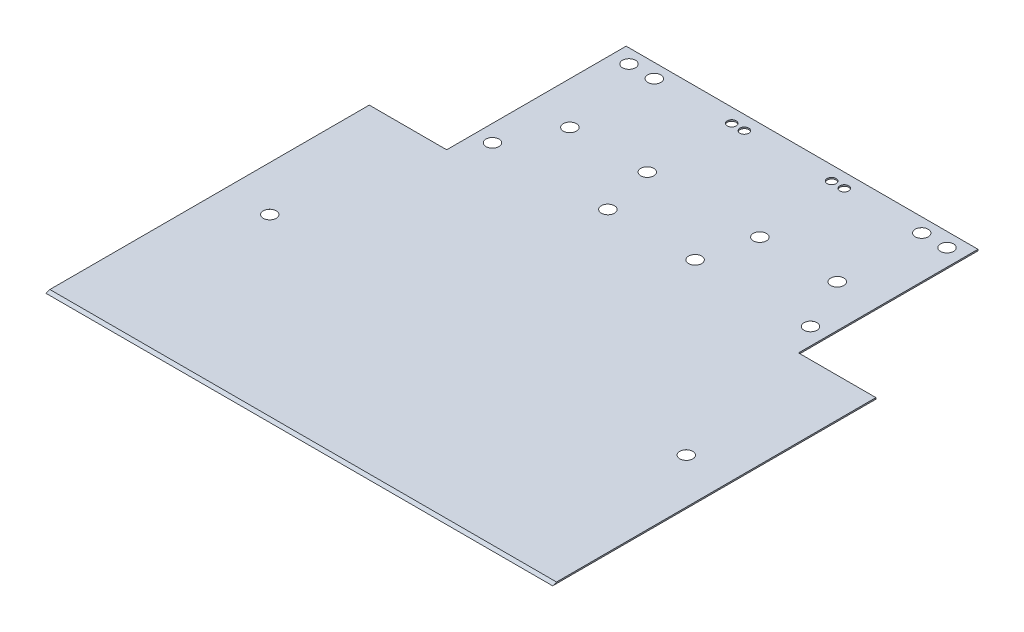
SolidWorks part; units mm, degrees
ref_plane "Alzado" through (0, 0, 0) normal (0, 0, 1) x (1, 0, 0)
ref_plane "Planta" through (0, 0, 0) normal (0, 1, 0) x (1, 0, 0)
ref_plane "Vista lateral" through (0, 0, 0) normal (1, 0, 0) x (0, 0, -1)
sketch "Croquis2" plane through (0, 0, 0) normal (0, 1, 0) x (1, 0, 0)
  line L0 (-90, 25.54) -> (-62.5, 25.54)
  line L1 (90, -89.31) -> (-90, -89.31)
  line L2 (90, -89.31) -> (90, 25.54)
  line L3 (62.5, 89.31) -> (-62.5, 89.31)
  line L4 (-90, -89.31) -> (-90, 25.54)
  line L5 (90, -89.31) -> (-62.5, 62.0208) construction
  line L6 (62.5, 62.0208) -> (-90, -89.31) construction
  line L7 (-62.5, 25.54) -> (-62.5, 89.31)
  line L8 (0, 0) -> (0, 89.31) construction
  line L9 (90, 25.54) -> (62.5, 25.54)
  line L10 (62.5, 25.54) -> (62.5, 89.31)
  point P0 (0, 0)
  dimension "D1" = 125
  dimension "D2" = 180
  dimension "D4" = 63.77
extrude "Saliente-Extruir1" add sketch "Croquis2" along normal blind 0.5
sketch "Croquis3" plane through (90, 0, 0) normal (1, 0, 0) x (0, 0, -1)
  line L0 (-89.31, 0) -> (-87.9363, 0.5)
  line L1 (-89.31, 0.5) -> (25.54, 0.5) construction
  line L2 (-87.9363, 0.5) -> (-89.31, 0.5)
  line L3 (-89.31, 0.5) -> (-89.31, 0)
  dimension "D1" = 70
sketch "Croquis5" plane through (0, 0.5, 0) normal (0, 1, 0) x (1, 0, 0)
  circle A0 centre (74, -25.8204) radius 1.585
sketch "Croquis6" plane through (0, 0.5, 0) normal (0, 1, 0) x (1, 0, 0)
  circle A0 centre (-56.5, 35.81) radius 1.585
  circle A1 centre (-15.5, 35.81) radius 1.585
  circle A2 centre (-15.5, 84.31) radius 1.585
  circle A3 centre (-56.5, 84.31) radius 1.585
extrude "Cortar-Extruir4" cut sketch "Croquis6" against normal up to next
sketch "Croquis7" plane through (0, 0.5, 0) normal (0, 1, 0) x (1, 0, 0)
  circle A0 centre (56.5, 35.81) radius 1.585
  circle A1 centre (15.5, 35.81) radius 1.585
  circle A2 centre (15.5, 84.31) radius 1.585
  circle A3 centre (56.5, 84.31) radius 1.585
extrude "Cortar-Extruir5" cut sketch "Croquis7" against normal up to next
mirror "Simetría3" about plane through (0, 0, 0) normal (1, 0, 0) of "Saliente-Extruir1"
sketch "Croquis8" plane through (0, 0.5, 0) normal (0, 1, 0) x (1, 0, 0)
  circle A0 centre (-20, 54.31) radius 1.585
  circle A1 centre (-47.5, 54.31) radius 1.585
  circle A2 centre (-47.5, 84.31) radius 1.585
  circle A3 centre (-20, 84.31) radius 1.585
extrude "Cortar-Extruir6" cut sketch "Croquis8" against normal up to next
mirror "Simetría4" about plane through (0, 0, 0) normal (1, 0, 0) of "Cortar-Extruir6"
sketch "Croquis9" plane through (0, 0, 0) normal (0, -1, 0) x (1, 0, 0)
  circle A0 centre (56.5, -35.81) radius 1.585
  circle A2 centre (15.5, -35.81) radius 1.585
  circle A3 centre (15.5, -84.31) radius 1.585
  circle A4 centre (56.5, -84.31) radius 1.585
extrude "Cortar-Extruir7" cut sketch "Croquis9" against normal up to next
mirror "Simetría5" about plane through (0, 0, 0) normal (1, 0, 0) of "Cortar-Extruir7"
extrude "Cortar-Extruir8" cut sketch "Croquis5" against normal up to next
mirror "Simetría6" about plane through (0, 0, 0) normal (1, 0, 0) of "Cortar-Extruir8"
extrude "Cortar-Extruir9" cut sketch "Croquis3" against normal up to next
sketch "Croquis11" plane through (0, 0, 0) normal (0, -1, 0) x (1, 0, 0)
  circle A0 centre (-74, 25.8204) radius 3.03
  circle A1 centre (-56.5, -35.81) radius 3.03
  circle A2 centre (-15.5, -35.81) radius 3.03
  circle A3 centre (-20, -54.31) radius 3.03
  circle A4 centre (-47.5, -54.31) radius 3.03
  circle A5 centre (-47.5, -84.31) radius 3.03
  circle A6 centre (-56.5, -84.31) radius 3.03
  dimension "D1" = 6.06
  dimension "D2" = 6.06
  dimension "D3" = 6.06
  dimension "D4" = 6.06
  dimension "D5" = 6.06
  dimension "D6" = 6.06
  dimension "D7" = 6.06
extrude "Cortar-Extruir10" cut sketch "Croquis11" against normal blind 1 draft 55
mirror "Simetría7" about plane through (0, 0, 0) normal (1, 0, 0) of "Cortar-Extruir10"
